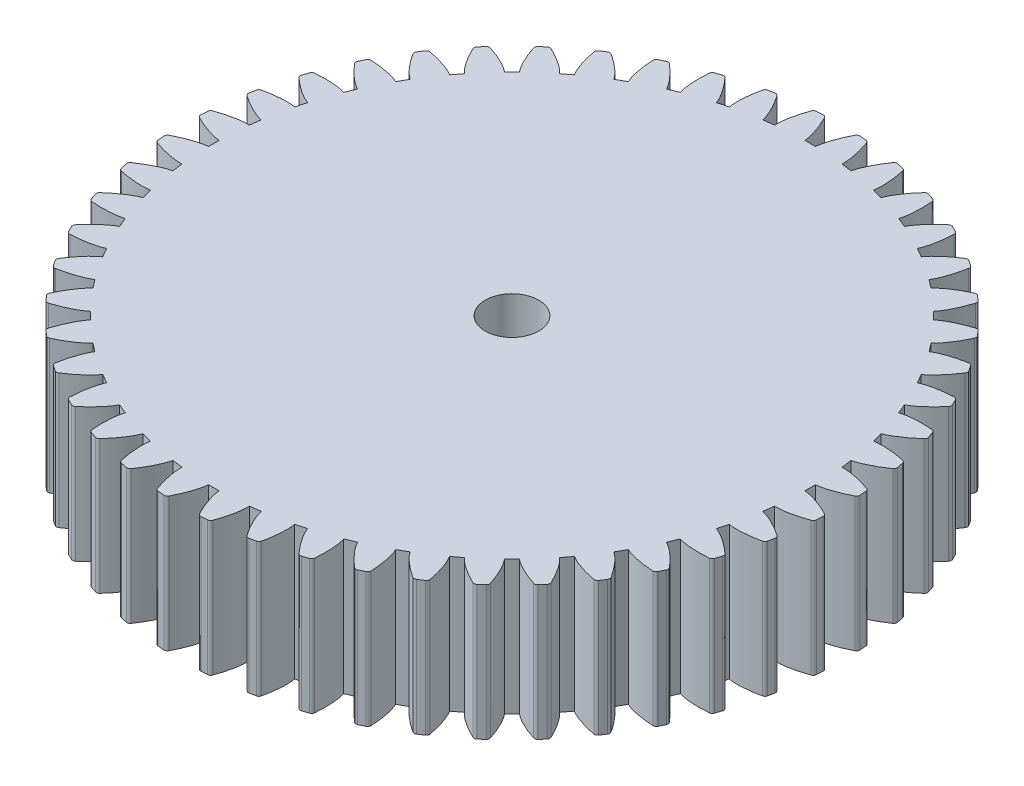
SolidWorks part; units mm, degrees
ref_plane "Front Plane" through (0, 0, 0) normal (0, 0, 1) x (1, 0, 0)
ref_plane "Top Plane" through (0, 0, 0) normal (0, 1, 0) x (1, 0, 0)
ref_plane "Right Plane" through (0, 0, 0) normal (1, 0, 0) x (0, 0, -1)
sketch "Sketch1" plane through (0, 0, 0) normal (0, 1, 0) x (1, 0, 0)
  circle A0 centre (0, 0) radius 25.019
  dimension "D1" = 50.038
extrude "Boss-Extrude1" add sketch "Sketch1" along normal blind 10.16 contours A0
sketch "Sketch2" plane through (0, 10.16, 0) normal (0, 1, 0) x (1, 0, 0)
  circle A0 centre (0, 0) radius 2.032
  dimension "D1" = 4.064
extrude "Cut-Extrude1" cut sketch "Sketch2" against normal through all contours A0
sketch "Sketch3" plane through (0, 10.16, 0) normal (0, 1, 0) x (1, 0, 0)
  line L0 (0, 0) -> (33.2639, 0) construction
  line L1 (25.0221, 1.2502) -> (25.0221, -1.2502)
  circle A0 centre (0, 0) radius 22.86 construction
  circle A1 centre (0, 0) radius 22.606 construction
  circle A2 centre (0, 0) radius 24.003 construction
  arc A3 (22.6024, 0.4028) -> (22.6024, -0.4028) centre (0, 0) cw
  spline S0 degree 4 poles (22.6024, 0.4028) (22.6062, 0.4029) (22.6169, 0.4034) (22.6371, 0.4046) (22.6701, 0.4074) (22.7121, 0.4118) (22.7663, 0.4187) (22.8301, 0.4283) (22.9002, 0.4404) (22.9764, 0.4552) (23.0523, 0.4714) (23.128, 0.4889) (23.2034, 0.5076) (23.2946, 0.5317) (23.4038, 0.5626) (23.5313, 0.6016) (23.6757, 0.6494) (23.8226, 0.7018) (23.967, 0.7564) (24.1126, 0.815) (24.2533, 0.8743) (24.3992, 0.9394) (24.5337, 1.0014) (24.6841, 1.0748) (24.8053, 1.1352) (24.9649, 1.2191) (25.059, 1.27) (25.1691, 1.3309) (25.2179, 1.3588) (25.2479, 1.3759) knots 0 0 0 0 0 0.005377 0.015084 0.028532 0.04661 0.064855 0.092111 0.119476 0.146842 0.174209 0.201575 0.228941 0.256307 0.307035 0.361767 0.4165 0.471232 0.525964 0.580697 0.635429 0.690161 0.744894 0.799626 0.854358 0.909091 0.954545 1 1 1 1 1 construction
  spline S1 degree 4 poles (22.6024, 0.4028) (22.6062, 0.4029) (22.6169, 0.4034) (22.6371, 0.4046) (22.6701, 0.4074) (22.7121, 0.4118) (22.7663, 0.4187) (22.8301, 0.4283) (22.9002, 0.4404) (22.9764, 0.4552) (23.0523, 0.4714) (23.128, 0.4889) (23.2034, 0.5076) (23.2946, 0.5317) (23.4038, 0.5626) (23.5313, 0.6016) (23.6757, 0.6494) (23.8226, 0.7018) (23.967, 0.7564) (24.1126, 0.815) (24.2533, 0.8743) (24.3992, 0.9394) (24.5337, 1.0014) (24.6841, 1.0748) (24.8053, 1.1352) (24.9303, 1.2009) (24.9911, 1.2334) (25.0221, 1.2502) knots 0 0 0 0 0 0.005377 0.015084 0.028532 0.04661 0.064855 0.092111 0.119476 0.146842 0.174209 0.201575 0.228941 0.256307 0.307035 0.361767 0.4165 0.471232 0.525964 0.580697 0.635429 0.690161 0.744894 0.799626 0.854358 0.909091 0.909091 0.909091 0.909091 0.909091
  spline S2 degree 4 poles (22.6024, -0.4028) (22.6062, -0.4029) (22.6169, -0.4034) (22.6371, -0.4046) (22.6701, -0.4074) (22.7121, -0.4118) (22.7663, -0.4187) (22.8301, -0.4283) (22.9002, -0.4404) (22.9764, -0.4552) (23.0523, -0.4714) (23.128, -0.4889) (23.2034, -0.5076) (23.2946, -0.5317) (23.4038, -0.5626) (23.5313, -0.6016) (23.6757, -0.6494) (23.8226, -0.7018) (23.967, -0.7564) (24.1126, -0.815) (24.2533, -0.8743) (24.3992, -0.9394) (24.5337, -1.0014) (24.6841, -1.0748) (24.8053, -1.1352) (24.9303, -1.2009) (24.9911, -1.2334) (25.0221, -1.2502) knots 0 0 0 0 0 0.005377 0.015084 0.028532 0.04661 0.064855 0.092111 0.119476 0.146842 0.174209 0.201575 0.228941 0.256307 0.307035 0.361767 0.4165 0.471232 0.525964 0.580697 0.635429 0.690161 0.744894 0.799626 0.854358 0.909091 0.909091 0.909091 0.909091 0.909091
  dimension "D1" = 45.72
  dimension "D2" = 45.212
  dimension "D3" = 48.006
extrude "Cut-Extrude2" cut sketch "Sketch3" against normal through all
fillet "Fillet1" radius 0.254 2 edges at (24.9886, 5.08, 1.2322) (24.9886, 5.08, -1.2322)
pattern_circular "CirPattern1" count 48 over 360 about axis through (0, 10.16, 0) along (0, 1, 0) of "Fillet1", "Cut-Extrude2"
equation "\"P\"= 25.4'INPUT: diameteral pitch"
equation "\"z\"= 48'INPUT: number of teeth"
equation "\"a\"= 20'INPUT: pressure angle, degrees"
equation "\"s\"= 0.4'INPUT: face width (inches)"
equation "\"D_b\"= 0.16'INPUT: gear bore diameter (inches)"
equation "\"c\"= 0.157 / \"P\"'clearance"
equation "\"D_p\"= \"z\" / \"P\"'pitch circle diameter"
equation "\"D_base\"= \"D_p\" * cos ( \"a\" )'base circle diameter"
equation "\"h_a\"= 1 / \"P\"'addendum depth"
equation "\"h_d\"= 1 / \"P\" + \"c\"'dedendum depth"
equation "\"P_c\"= pi / \"P\"'circular pitch"
equation "\"D_a\"= \"D_p\" + ( 2 * \"h_a\" )'addendum diameter"
equation "\"D_d\"= \"D_p\" - ( 2 * \"h_d\" )'dedendum diameter"
equation "\"theta\"= 360 / \"z\"'pitch angle"
equation "\"a_inv\"= ( \"D_p\" ^ 2 - \"D_base\" ^ 2 ) ^ 0.5 / \"D_base\" * 180 / pi - \"a\"'alpha angle for involute curve"
equation "\"b_inv\"= ( \"theta\" / 4 - \"a_inv\" )'beta angle (parameter for ivolute curve parameterization)"
equation "\"zeta\"= ( ( \"D_a\" / 2 ) ^ 2 - ( \"D_base\" / 2 ) ^ 2 ) ^ 0.5 / ( \"D_base\" / 2 )'zeta (domain for involute curve equation)"
